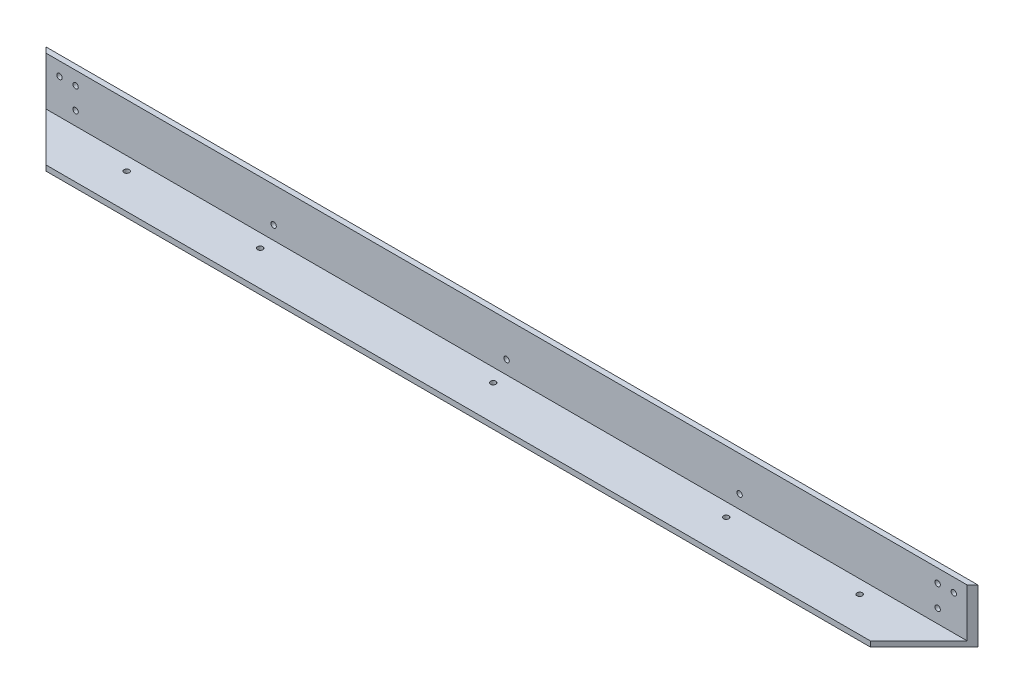
SolidWorks part; units mm, degrees
ref_plane "Front Plane" through (0, 0, 0) normal (0, 0, 1) x (1, 0, 0)
ref_plane "Top Plane" through (0, 0, 0) normal (0, 1, 0) x (1, 0, 0)
ref_plane "Right Plane" through (0, 0, 0) normal (1, 0, 0) x (0, 0, -1)
sketch "Sketch1" plane through (0, 0, 0) normal (1, 0, 0) x (0, 0, -1)
  line L0 (0, 0) -> (-31.75, 0)
  line L1 (-31.75, 0) -> (-31.75, 3.175)
  line L2 (-31.75, 3.175) -> (-3.175, 3.175)
  line L3 (-3.175, 3.175) -> (-3.175, 31.75)
  line L4 (-3.175, 31.75) -> (0, 31.75)
  line L5 (0, 31.75) -> (0, 0)
  dimension "LHeight" = 31.75
  dimension "LWidth" = 31.75
  dimension "LMaterialThickness" = 3.175
  dimension "D1" = 28.575
  dimension "D2" = 28.575
  dimension "D3" = 3.175
extrude "Boss-Extrude1" add sketch "Sketch1" along normal blind 550
chamfer "Chamfer6" distance 31.75 angle 45 1 edges at (550, 1.5875, 31.75)
chamfer "Chamfer7" distance 31.75 angle 45 1 edges at (0, 1.5875, 31.75)
sketch "TopHoles-Sketch3" plane through (0, 3.175, 0) normal (0, 1, 0) x (1, 0, 0)
  line L0 (550, 0) -> (0, 0) construction
  circle A9 centre (491.2625, -11.1125) radius 1.5875
  circle A10 centre (58.7375, -11.1125) radius 1.5875
  circle A13 centre (137.5, -11.1125) radius 1.5875
  circle A14 centre (275, -11.1125) radius 1.5875
  circle A15 centre (412.5, -11.1125) radius 1.5875
  point P11 (53.4265, -17.2006)
  dimension "D8" = 137.5
  dimension "D10" = 137.5
  dimension "D5" = 3.175
  dimension "D11" = 137.5
  dimension "D2" = 11.1125
  dimension "D3" = 58.7375
  dimension "D4" = 58.7375
extrude "TopHoles-Cut-Extrude2" cut sketch "TopHoles-Sketch3" against normal through all
sketch "RightHoles-Sketch4" plane through (0, 0, 3.175) normal (0, 0, 1) x (1, 0, 0)
  line L1 (550, 0) -> (0, 0) construction
  line L3 (550, 31.75) -> (0, 31.75) construction
  line L4 (0, 0) -> (0, 31.75) construction
  line L5 (550, 0) -> (550, 31.75) construction
  circle A1 centre (11.1125, 23.8125) radius 1.5875
  circle A3 centre (529.3625, 23.8125) radius 1.5875
  circle A4 centre (20.6375, 23.8125) radius 1.5875
  circle A5 centre (538.8875, 23.8125) radius 1.5875
  circle A7 centre (20.6375, 11.1125) radius 1.5875
  circle A8 centre (529.3625, 11.1125) radius 1.5875
  circle A10 centre (137.5, 11.1125) radius 1.5875
  circle A11 centre (275, 11.1125) radius 1.5875
  circle A12 centre (412.5, 11.1125) radius 1.5875
  dimension "D2" = 3.175
  dimension "D4" = 7.9375
  dimension "D1" = 11.1125
  dimension "D6" = 20.6375
  dimension "D3" = 11.1125
  dimension "D5" = 20.6375
  dimension "D8" = 137.5
  dimension "D9" = 137.5
  dimension "D10" = 137.5
  dimension "D7" = 11.1125
extrude "RightHoles-Cut-Extrude3" cut sketch "RightHoles-Sketch4" against normal through all
equation "\"TopRailWidth\"= 1.25in"
equation "\"TopRailHeight\"= 1.25in"
equation "\"RailThickness\"= .125in'Spec"
equation "\"SideRailHoleY1FromEdge\"= \"HoleOffsetFromEdge\""
equation "\"SideRailHoleX1FromSide\"= \"HoleOffsetFromSide\""
equation "\"SideRailLength\"= 550mm"
equation "\"VSWidth\"= 1.25in'Spec"
equation "\"HoleOffsetFromEdge\"= \"RailThickness\" * 2.5"
equation "\"HoleOffsetFromSide\"= \"RailThickness\" * 3.5"
equation "\"TopHoleY1FromSide\"= \"HoleOffsetFromSide\""
equation "\"SideRailHoleX2FromSide\"= \"VSWidth\" - \"HoleOffsetFromEdge\" - \"RailThickness\"'Equals 20.6375"
equation "\"FasteningHoleDiameter\"= .125in"
equation "\"SideRailHoleY2FromSide\"= \"HoleOffsetFromSide\""
equation "\"D2@RightHoles-Sketch4\"=\"FasteningHoleDiameter\""
equation "\"LWidth@Sketch1\"=\"TopRailWidth\""
equation "\"LHeight@Sketch1\"=\"TopRailHeight\""
equation "\"LMaterialThickness@Sketch1\"=\"RailThickness\""
equation "\"D1@Boss-Extrude1\"=\"SideRailLength\""
equation "\"D4@RightHoles-Sketch4\"=\"SideRailHoleY1FromEdge\""
equation "\"D1@Chamfer6\"=\"TopRailWidth\""
equation "\"D1@Chamfer7\"=\"TopRailWidth\""
equation "\"D1@RightHoles-Sketch4\"=\"SideRailHoleX1FromSide\""
equation "\"D6@RightHoles-Sketch4\"=\"SideRailHoleX2FromSide\""
equation "\"D3@RightHoles-Sketch4\"=\"SideRailHoleX1FromSide\""
equation "\"D5@RightHoles-Sketch4\"=\"SideRailHoleX2FromSide\""
equation "\"TopCBLength\"= \"TopRailWidth\" * 2'Equals 63.5"
equation "\"LeftOrRightEnclosureOffsets\"= \"SideRailLength\" / 4"
equation "\"D8@TopHoles-Sketch3\"=\"LeftOrRightEnclosureOffsets\""
equation "\"D10@TopHoles-Sketch3\"=\"LeftOrRightEnclosureOffsets\""
equation "\"D11@TopHoles-Sketch3\"=\"LeftOrRightEnclosureOffsets\""
equation "\"D8@RightHoles-Sketch4\"=\"LeftOrRightEnclosureOffsets\""
equation "\"D9@RightHoles-Sketch4\"=\"LeftOrRightEnclosureOffsets\""
equation "\"D10@RightHoles-Sketch4\"=\"LeftOrRightEnclosureOffsets\""
equation "\"D7@RightHoles-Sketch4\"=\"SideRailHoleY2FromSide\""
equation "\"LeftOrRightCornerEnclosureOffset\"= \"RailThickness\" + \"TopCBLength\" - \"HoleOffsetFromEdge\"'Equals 58.7375"
equation "\"D2@TopHoles-Sketch3\"=\"TopHoleY1FromSide\""
equation "\"D3@TopHoles-Sketch3\"=\"LeftOrRightCornerEnclosureOffset\""
equation "\"D4@TopHoles-Sketch3\"=\"LeftOrRightCornerEnclosureOffset\""
equation "\"D5@TopHoles-Sketch3\"=\"FasteningHoleDiameter\""
